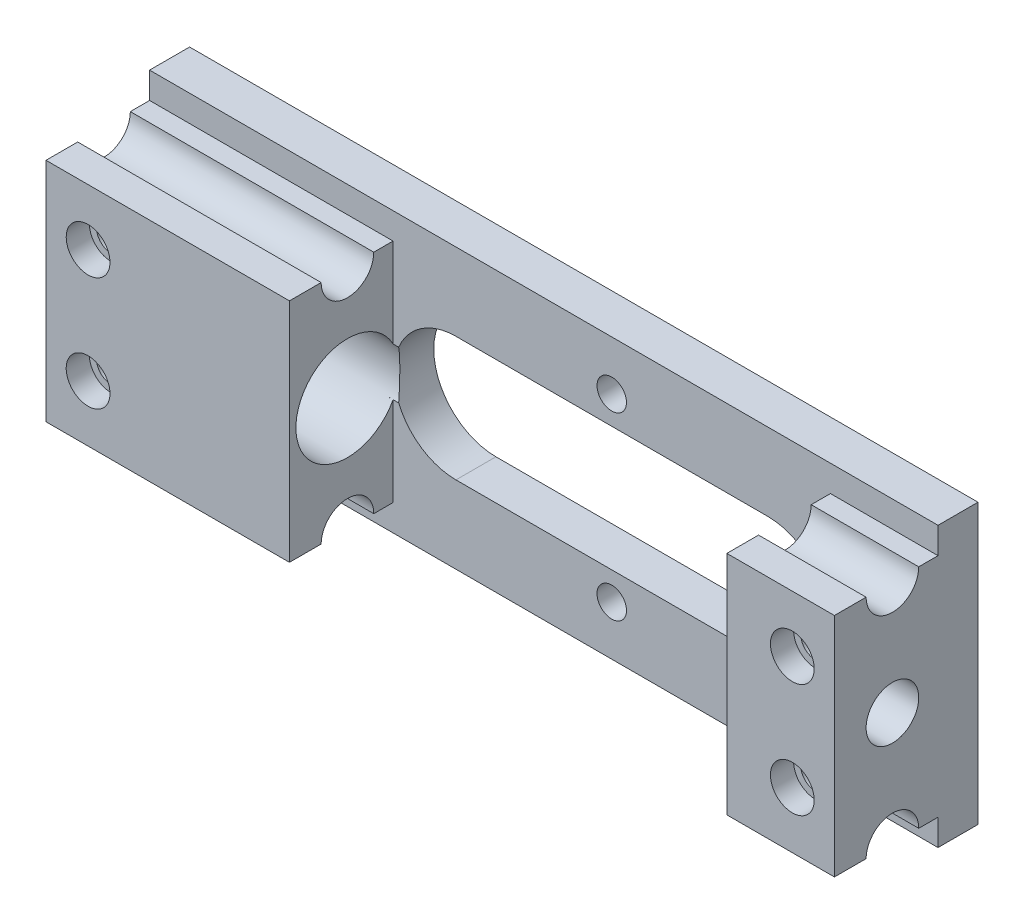
SolidWorks part; units mm, degrees
ref_plane "Front Plane" through (0, 0, 0) normal (0, 0, 1) x (1, 0, 0)
ref_plane "Top Plane" through (0, 0, 0) normal (0, 1, 0) x (1, 0, 0)
ref_plane "Right Plane" through (0, 0, 0) normal (1, 0, 0) x (0, 0, -1)
sketch "Sketch1" plane through (0, 0, 0) normal (0, 0, 1) x (1, 0, 0)
  line L1 (-22.0345, -8.4201) -> (22.0345, -8.4201)
  line L2 (-22.0345, -8.4201) -> (-22.0345, 8.4201)
  line L3 (-22.0345, 8.4201) -> (22.0345, 8.4201)
  line L4 (22.0345, -8.4201) -> (22.0345, 8.4201)
  line L5 (-22.0345, -8.4201) -> (22.0345, 8.4201) construction
  line L6 (-22.0345, 8.4201) -> (22.0345, -8.4201) construction
  point P0 (0, 0)
  dimension "D1" = 44.069
  dimension "D2" = 16.8402
extrude "Boss-Extrude1" add sketch "Sketch1" along normal blind 7.1628
sketch "Sketch2" plane through (0, 0, 7.1628) normal (0, 0, 1) x (1, 0, 0)
  line L0 (-22.0345, 0) -> (22.0345, 0) construction
  line L1 (-10.8458, 8.4201) -> (15.5448, 8.4201)
  line L2 (-10.8458, 8.4201) -> (-10.8458, -8.4201)
  line L3 (-10.8458, -8.4201) -> (15.5448, -8.4201)
  line L4 (15.5448, 8.4201) -> (15.5448, -8.4201)
  line L5 (-22.0345, 8.4201) -> (-22.0345, -8.4201) construction
  line L6 (22.0345, -8.4201) -> (22.0345, 8.4201) construction
  line L7 (-10.8458, 8.4201) -> (-22.0345, 0) construction
  line L8 (-22.0345, 0) -> (-10.8458, -8.4201) construction
  line L9 (2.3495, 8.4201) -> (2.3495, -8.4201) construction
  line L12 (22.0345, 8.4201) -> (-22.0345, 8.4201) construction
  dimension "D1" = 26.3906
  dimension "D2" = 24.384
extrude "Cut-Extrude1" cut sketch "Sketch2" against normal blind 4.75
sketch "Sketch4" plane through (0, 0, 7.1628) normal (0, 0, 1) x (1, 0, 0)
  line L0 (-10.8458, 8.4201) -> (-10.8458, -8.4201) construction
  line L1 (-22.0345, -8.4201) -> (-10.8458, -8.4201)
  line L2 (-22.0345, -8.4201) -> (-22.0345, -6.8326)
  line L3 (-22.0345, -6.8326) -> (-10.8458, -6.8326)
  line L4 (-10.8458, -8.4201) -> (-10.8458, -6.8326)
  line L5 (-22.0345, 0) -> (-10.8458, 0) construction
  line L6 (-22.0345, 8.4201) -> (-22.0345, -8.4201) construction
  line L7 (-10.8458, 8.4201) -> (-10.8458, -8.4201) construction
  line L8 (-10.8458, 8.4201) -> (-10.8458, 6.8326)
  line L9 (-22.0345, 6.8326) -> (-10.8458, 6.8326)
  line L10 (-22.0345, 8.4201) -> (-22.0345, 6.8326)
  line L11 (-22.0345, 8.4201) -> (-10.8458, 8.4201)
  line L12 (22.0345, -8.4201) -> (22.0345, 8.4201) construction
  line L13 (15.5448, -8.4201) -> (22.0345, -8.4201)
  line L14 (15.5448, -8.4201) -> (15.5448, -6.8326)
  line L15 (15.5448, -6.8326) -> (22.0345, -6.8326)
  line L16 (22.0345, -8.4201) -> (22.0345, -6.8326)
  line L17 (15.5448, 6.8326) -> (22.0345, 6.8326)
  line L18 (22.0345, 8.4201) -> (22.0345, 6.8326)
  line L19 (15.5448, 8.4201) -> (22.0345, 8.4201)
  line L20 (15.5448, 8.4201) -> (15.5448, 6.8326)
  dimension "D1" = 1.5875
extrude "Cut-Extrude9" cut sketch "Sketch4" against normal up to surface (4.75 mm away) up to face at (2.3495, 0, 2.4128)
sketch "Sketch5" plane through (-22.0345, 0, 0) normal (-1, 0, 0) x (0, 0, 1)
  line L1 (0, 0) -> (7.1628, 0) construction
  line L2 (0, 8.4201) -> (0, -8.4201) construction
  line L3 (7.1628, 6.8326) -> (7.1628, -6.8326) construction
  circle A0 centre (5.1628, -6.8326) radius 1.5875
  circle A1 centre (5.1628, 6.8326) radius 1.5875
  dimension "D1" = 3.175
  dimension "D2" = 2
extrude "Cut-Extrude10" cut sketch "Sketch5" against normal through all
sketch "Sketch14" plane through (0, 0, 7.1628) normal (0, 0, 1) x (1, 0, 0)
  line L4 (-10.8458, -6.8326) -> (-10.8458, 6.8326)
  line L5 (-10.8458, 6.8326) -> (-22.0345, 6.8326)
  line L6 (-22.0345, 6.8326) -> (-22.0345, -6.8326)
  line L7 (-22.0345, -6.8326) -> (-10.8458, -6.8326)
  line L8 (-10.8458, -6.8326) -> (-10.8458, 6.8326)
  line L9 (-10.8458, 6.8326) -> (-22.0345, 6.8326)
  line L10 (-22.0345, 6.8326) -> (-22.0345, -6.8326)
  line L11 (-22.0345, -6.8326) -> (-10.8458, -6.8326)
  line L12 (22.0345, -6.8326) -> (22.0345, 6.8326)
  line L13 (22.0345, 6.8326) -> (15.5448, 6.8326)
  line L14 (15.5448, 6.8326) -> (15.5448, -6.8326)
  line L15 (15.5448, -6.8326) -> (22.0345, -6.8326)
  line L16 (22.0345, -6.8326) -> (22.0345, 6.8326)
  line L17 (22.0345, 6.8326) -> (15.5448, 6.8326)
  line L18 (15.5448, 6.8326) -> (15.5448, -6.8326)
  line L19 (15.5448, -6.8326) -> (22.0345, -6.8326)
  dimension "D1" = 0
  dimension "D2" = 0
extrude "Boss-Extrude3" add sketch "Sketch14" along normal blind 1.5
sketch "Sketch6" plane through (0, 0, 8.6628) normal (0, 0, 1) x (1, 0, 0)
  line L0 (-22.0345, 0) -> (-10.8458, 0) construction
  line L2 (-10.8458, 6.8326) -> (-10.8458, -6.8326) construction
  line L3 (-22.0345, 6.8326) -> (-22.0345, -6.8326) construction
  circle A0 centre (-14.7955, 3.429) radius 0.889
  circle A1 centre (-14.7955, -3.429) radius 0.889
  circle A2 centre (19.4945, 3.429) radius 0.889
  circle A3 centre (19.4945, -3.429) radius 0.889
  dimension "D1" = 1.778
  dimension "D2" = 6.858
  dimension "D3" = 7.239
  dimension "D4" = 2
extrude "Cut-Extrude11" cut sketch "Sketch6" against normal through all contours A2 | A3 region at (19.4945, 3.429, 8.6628) region at (19.4945, -3.429, 8.6628)
sketch "Sketch7" plane through (0, 0, 8.6628) normal (0, 0, 1) x (1, 0, 0)
  circle A2 centre (19.4945, 3.429) radius 1.3208
  circle A3 centre (19.4945, -3.429) radius 1.3208
extrude "Cut-Extrude12" cut sketch "Sketch7" against normal blind 1.397
sketch "Sketch9" plane through (0, 0, 0) normal (0, 0, -1) x (-1, 0, 0)
  line L0 (22.0345, 8.4201) -> (22.0345, -8.4201) construction
  line L1 (-22.0345, 0) -> (22.0345, 0) construction
  line L2 (-22.0345, -8.4201) -> (-22.0345, 8.4201) construction
  circle A0 centre (-2.3495, 5.4356) radius 0.889
  circle A1 centre (-2.3495, -5.4356) radius 0.889
  dimension "D1" = 1.778
  dimension "D2" = 24.384
  dimension "D3" = 10.8712
extrude "Cut-Extrude13" cut sketch "Sketch9" against normal through all
sketch "Sketch10" plane through (0, 0, 0) normal (0, 0, -1) x (-1, 0, 0)
  line L0 (-22.0345, 0) -> (22.0345, 0) construction
  line L1 (-22.0345, -8.4201) -> (-22.0345, 8.4201) construction
  line L2 (22.0345, 8.4201) -> (22.0345, -8.4201) construction
  circle A0 centre (-2.3495, 5.4356) radius 1.1906
  circle A1 centre (-2.3495, -5.4356) radius 1.1906
  dimension "D1" = 2.3813
extrude "Cut-Extrude14" cut sketch "Sketch10" against normal blind 1
sketch "Sketch11" plane through (0, 0, 0) normal (0, 0, -1) x (-1, 0, 0)
  line L0 (-22.0345, 0) -> (22.0345, 0) construction
  line L1 (-22.0345, -8.4201) -> (-22.0345, 8.4201) construction
  line L2 (22.0345, 8.4201) -> (22.0345, -8.4201) construction
  line L3 (-2.3495, 5.4356) -> (-2.3495, -5.4356) construction
  line L4 (-11.7495, 0) -> (7.0505, 0) construction
  line L5 (-11.7495, 3.75) -> (7.0505, 3.75)
  line L6 (-11.7495, -3.75) -> (7.0505, -3.75)
  arc A0 (-11.7495, 3.75) -> (-11.7495, -3.75) centre (-11.7495, 0) ccw
  arc A1 (7.0505, -3.75) -> (7.0505, 3.75) centre (7.0505, 0) ccw
  point P12 (-2.3495, 0)
  dimension "D1" = 7.5
  dimension "D2" = 18.8
extrude "Cut-Extrude15" cut sketch "Sketch11" against normal through all
sketch "Sketch12" plane through (-10.8458, 0, 0) normal (1, 0, 0) x (0, 0, -1)
  circle A0 centre (-5.1628, 0) radius 3.1115
  dimension "D1" = 6.223
extrude "Cut-Extrude16" cut sketch "Sketch12" against normal blind 10.922 and the other way up to next
sketch "Sketch15" plane through (-22.0345, 0, 0) normal (-1, 0, 0) x (0, 0, 1)
  line L10 (8.6628, 6.8326) -> (6.7503, 6.8326)
  line L11 (3.5753, 6.8326) -> (2.4128, 6.8326)
  line L12 (2.4128, 6.8326) -> (2.4128, 8.4201)
  line L13 (2.4128, 8.4201) -> (0, 8.4201)
  line L14 (0, 8.4201) -> (0, -8.4201)
  line L15 (0, -8.4201) -> (2.4128, -8.4201)
  line L16 (2.4128, -8.4201) -> (2.4128, -6.8326)
  line L17 (2.4128, -6.8326) -> (3.5753, -6.8326)
  line L18 (6.7503, -6.8326) -> (8.6628, -6.8326)
  line L19 (8.6628, -6.8326) -> (8.6628, 6.8326)
  line L20 (8.6628, 6.8326) -> (6.7503, 6.8326)
  line L21 (3.5753, 6.8326) -> (2.4128, 6.8326)
  line L22 (2.4128, 6.8326) -> (2.4128, 8.4201)
  line L23 (2.4128, 8.4201) -> (0, 8.4201)
  line L24 (0, 8.4201) -> (0, -8.4201)
  line L25 (0, -8.4201) -> (2.4128, -8.4201)
  line L26 (2.4128, -8.4201) -> (2.4128, -6.8326)
  line L27 (2.4128, -6.8326) -> (3.5753, -6.8326)
  line L28 (6.7503, -6.8326) -> (8.6628, -6.8326)
  line L29 (8.6628, -6.8326) -> (8.6628, 6.8326)
  arc A2 (3.5753, 6.8326) -> (6.7503, 6.8326) centre (5.1628, 6.8326) ccw
  arc A3 (6.7503, -6.8326) -> (3.5753, -6.8326) centre (5.1628, -6.8326) ccw
  arc A4 (3.5753, 6.8326) -> (6.7503, 6.8326) centre (5.1628, 6.8326) ccw
  arc A5 (6.7503, -6.8326) -> (3.5753, -6.8326) centre (5.1628, -6.8326) ccw
  dimension "D1" = 0
extrude "Boss-Extrude4" add sketch "Sketch15" along normal blind 3.5
ref_plane "Plane1" through (-1.75, 0, 0) normal (1, 0, 0) x (0, 0, -1)
mirror "Mirror1" about plane through (-1.75, 0, 0) normal (1, 0, 0) of "Cut-Extrude11", "Cut-Extrude12"
sketch "Sketch16" plane through (22.0345, 0, 0) normal (1, 0, 0) x (0, 0, -1)
  circle A0 centre (-5.1628, 0) radius 1.5875
  dimension "D1" = 3.175
extrude "Cut-Extrude17" cut sketch "Sketch16" against normal up to next
